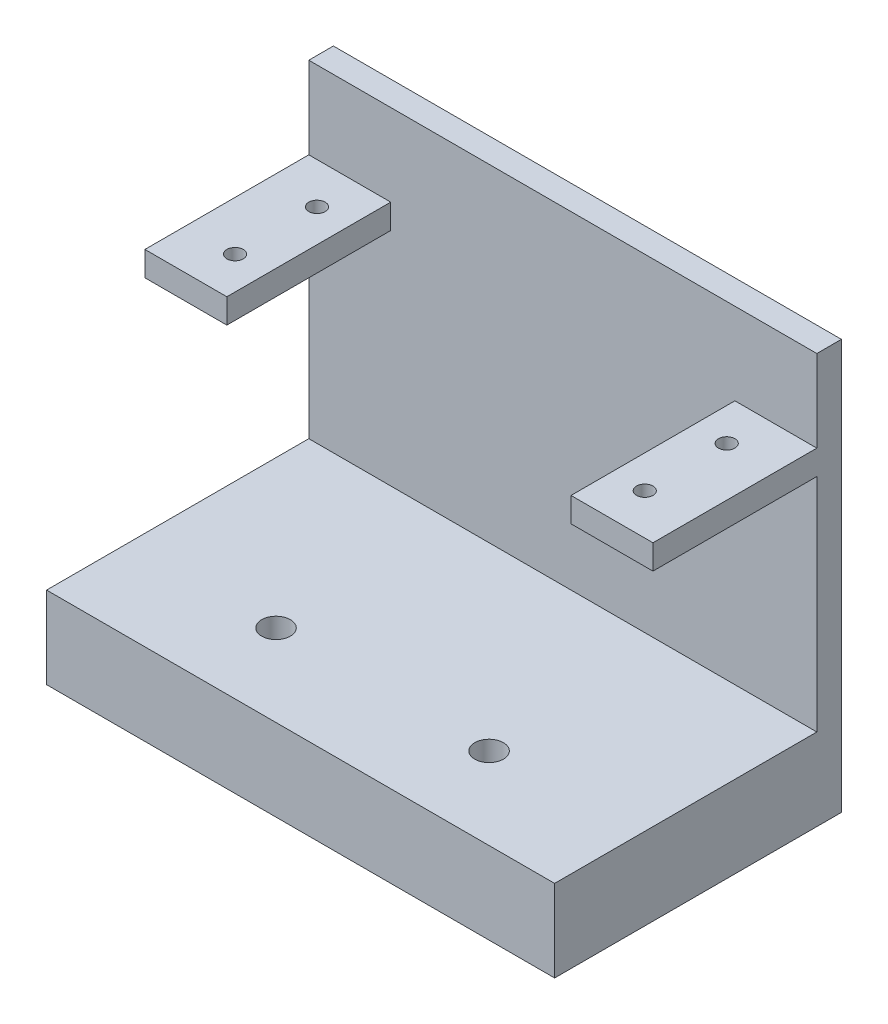
SolidWorks part; units mm, degrees
ref_plane "Front Plane" through (0, 0, 0) normal (0, 0, 1) x (1, 0, 0)
ref_plane "Top Plane" through (0, 0, 0) normal (0, 1, 0) x (1, 0, 0)
ref_plane "Right Plane" through (0, 0, 0) normal (1, 0, 0) x (0, 0, -1)
sketch "Sketch1" plane through (0, 0, 0) normal (0, 1, 0) x (1, 0, 0)
  line L1 (0, 0) -> (62, 0)
  line L2 (0, 0) -> (0, 35)
  line L3 (0, 35) -> (62, 35)
  line L4 (62, 0) -> (62, 35)
  dimension "D1" = 62
  dimension "D2" = 35
extrude "Boss-Extrude1" add sketch "Sketch1" along normal blind 50
sketch "Sketch2" plane through (62, 0, 0) normal (1, 0, 0) x (0, 0, -1)
  line L0 (0, 50) -> (0, 0) construction
  line L1 (0, 10) -> (32, 10)
  line L2 (32, 37) -> (32, 10)
  line L3 (32, 37) -> (12, 37)
  line L4 (12, 37) -> (12, 40)
  line L5 (0, 0) -> (35, 0) construction
  line L7 (35, 50) -> (35, 0) construction
  line L8 (12, 40) -> (32, 40)
  line L9 (32, 40) -> (32, 50)
  line L10 (0, 50) -> (35, 50) construction
  line L11 (32, 50) -> (0, 50)
  line L12 (0, 50) -> (0, 10)
  dimension "D1" = 10
  dimension "D2" = 3
  dimension "D3" = 40
  dimension "D4" = 3
  dimension "D5" = 23
  dimension "D6" = 3
extrude "Cut-Extrude3" cut sketch "Sketch2" against normal through all
sketch "Sketch4" plane through (0, 10, 0) normal (0, 1, 0) x (1, 0, 0)
  line L0 (0, 12) -> (62, 12) construction
  line L1 (10, 12) -> (52, 12)
  line L2 (10, 12) -> (10, 32)
  line L3 (10, 32) -> (52, 32)
  line L4 (52, 12) -> (52, 32)
  line L5 (0, 32) -> (62, 32) construction
  line L6 (0, 12) -> (0, 32) construction
  line L7 (62, 12) -> (62, 32) construction
  dimension "D1" = 10
  dimension "D2" = 10
extrude "Cut-Extrude5" cut sketch "Sketch4" along normal blind 40
sketch "Sketch5" plane through (0, 10, 0) normal (0, 1, 0) x (1, 0, 0)
  line L0 (0, 0) -> (62, 0) construction
  line L1 (0, 0) -> (0, 32) construction
  line L2 (62, 0) -> (62, 32) construction
  line L3 (0, 12) -> (0, 32) construction
  line L4 (0, 35) -> (0, 0) construction
  line L5 (62, 12) -> (62, 32) construction
  line L6 (0, 12) -> (10, 12) construction
  line L7 (0, 32) -> (10, 32) construction
  line L8 (52, 32) -> (62, 32) construction
  line L9 (52, 12) -> (62, 12) construction
  circle A1 centre (18, 10) radius 1.75
  circle A2 centre (44, 10) radius 1.75
  circle A3 centre (6, 17) radius 1
  circle A4 centre (6, 27) radius 1
  circle A5 centre (56, 17) radius 1
  circle A6 centre (56, 27) radius 1
  point P22 (0, 17.5)
  dimension "D5" = 3.5
  dimension "D6" = 3.5
  dimension "D10" = 2
  dimension "D11" = 2
  dimension "D12" = 2
  dimension "D13" = 2
  dimension "D1" = 10
  dimension "D2" = 10
  dimension "D3" = 18
  dimension "D4" = 18
  dimension "D14" = 6
  dimension "D15" = 6
  dimension "D16" = 6
  dimension "D17" = 6
  dimension "D18" = 5
  dimension "D19" = 5
  dimension "D20" = 5
  dimension "D21" = 5
extrude "Cut-Extrude7" cut sketch "Sketch5" against normal blind 100 contours A1 | A2 region at (18, 10, -10) region at (44, 10, -10)
sketch "Sketch6" plane through (0, 40, 0) normal (0, 1, 0) x (1, 0, 0)
  circle A0 centre (6, 27) radius 1 construction
  circle A1 centre (6, 17) radius 1 construction
  circle A2 centre (56, 17) radius 1 construction
  circle A3 centre (56, 27) radius 1 construction
  circle A4 centre (6, 27) radius 1
  circle A5 centre (6, 17) radius 1
  circle A6 centre (56, 17) radius 1
  circle A7 centre (56, 27) radius 1
extrude "Cut-Extrude8" cut sketch "Sketch6" against normal up to next
